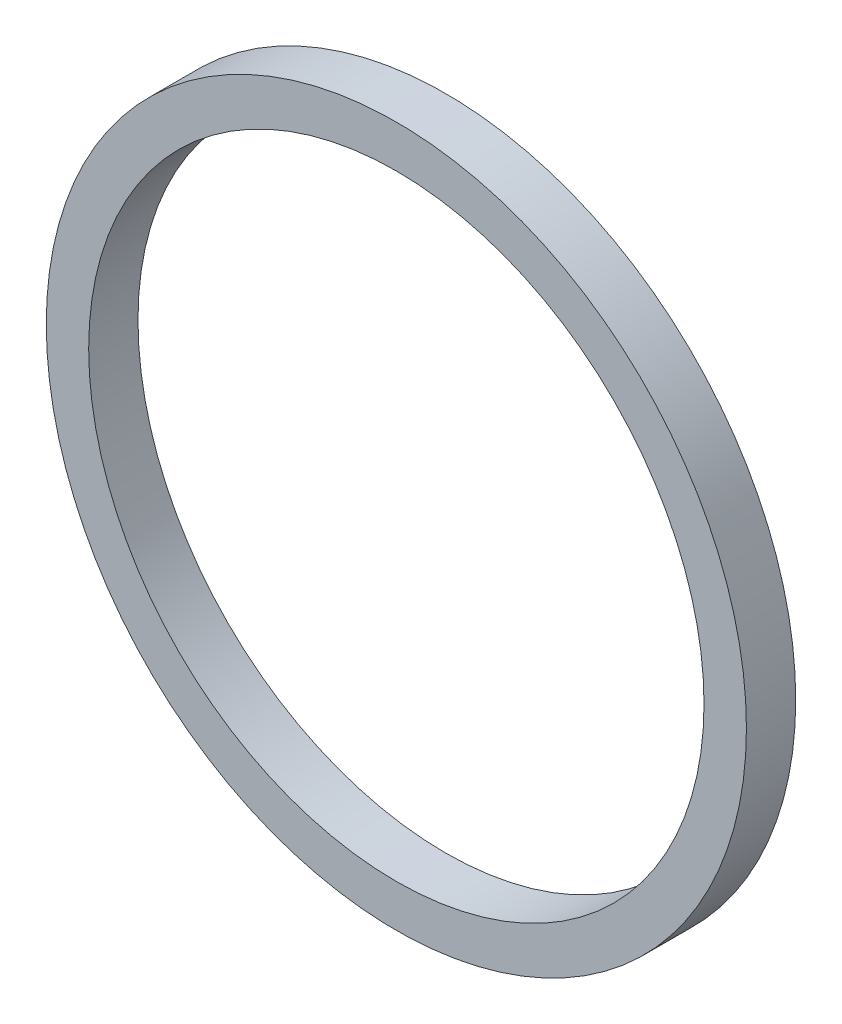
SolidWorks part; units mm, degrees
material "Plain Carbon Steel"
ref_plane "Front Plane" through (0, 0, 0) normal (0, 0, 1) x (1, 0, 0)
ref_plane "Top Plane" through (0, 0, 0) normal (0, 1, 0) x (1, 0, 0)
ref_plane "Right Plane" through (0, 0, 0) normal (1, 0, 0) x (0, 0, -1)
sketch "Sketch1" plane through (0, 0, 0) normal (0, 0, 1) x (1, 0, 0)
  circle A0 centre (0, 0) radius 22.5425
  circle A1 centre (0, 0) radius 19.812
  dimension "D1" = 45.085
  dimension "D2" = 39.624
extrude "Boss-Extrude1" add sketch "Sketch1" along normal blind 3.175
